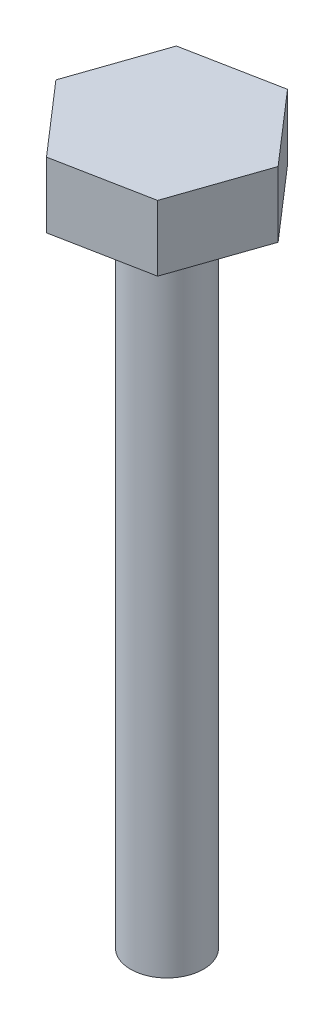
SolidWorks part; units mm, degrees
ref_plane "Front Plane" through (0, 0, 0) normal (0, 0, 1) x (1, 0, 0)
ref_plane "Top Plane" through (0, 0, 0) normal (0, 1, 0) x (1, 0, 0)
ref_plane "Right Plane" through (0, 0, 0) normal (1, 0, 0) x (0, 0, -1)
sketch "Sketch2" plane through (0, 0, 0) normal (0, 1, 0) x (1, 0, 0)
  line L1 (42.6271, -49.0707) -> (63.81, 12.3808)
  line L2 (63.81, 12.3808) -> (21.1829, 61.4515)
  line L3 (21.1829, 61.4515) -> (-42.6271, 49.0707)
  line L4 (-42.6271, 49.0707) -> (-63.81, -12.3808)
  line L5 (-63.81, -12.3808) -> (-21.1829, -61.4515)
  line L6 (-21.1829, -61.4515) -> (42.6271, -49.0707)
  circle A0 centre (0, 0) radius 56.2917 construction
  circle A1 centre (0, 0) radius 25
  dimension "D2" = 50
  dimension "D1" = 130
extrude "Boss-Extrude1" add sketch "Sketch2" along normal blind 45
extrude "Boss-Extrude2" add sketch "Sketch2<2>" along normal blind 45 and the other way blind 445 contours A1 region at (0, 0, 0)
sketch "Sketch2<2>" plane through (0, 0, 0) normal (0, 1, 0) x (1, 0, 0) same geometry as "Sketch2"
